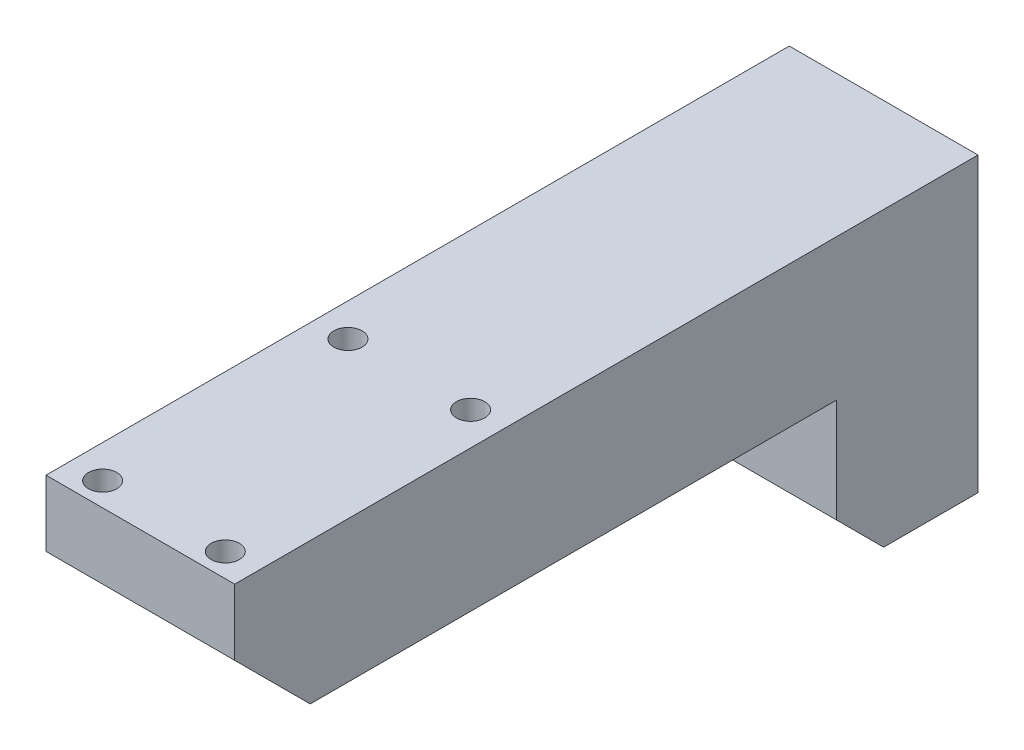
SolidWorks part; units mm, degrees
ref_plane "Płaszczyzna przednia" through (0, 0, 0) normal (0, 0, 1) x (1, 0, 0)
ref_plane "Płaszczyzna górna" through (0, 0, 0) normal (0, 1, 0) x (1, 0, 0)
ref_plane "Płaszczyzna prawa" through (0, 0, 0) normal (1, 0, 0) x (0, 0, -1)
sketch "Szkic1" plane through (0, 0, 0) normal (0, 1, 0) x (1, 0, 0)
  line L1 (20, -78.775) -> (-20, -78.775)
  line L2 (20, -78.775) -> (20, 78.775)
  line L3 (20, 78.775) -> (-20, 78.775)
  line L4 (-20, -78.775) -> (-20, 78.775)
  line L5 (20, -78.775) -> (-20, 78.775) construction
  line L6 (20, 78.775) -> (-20, -78.775) construction
  point P0 (0, 0)
  dimension "D1" = 40
  dimension "D2" = 157.55
extrude "Dodanie-wyciągnięcie1" add sketch "Szkic1" along normal blind 30
sketch "Szkic2" plane through (0, 0, 0) normal (0, -1, 0) x (-1, 0, 0)
  line L0 (20, 78.775) -> (20, -78.775) construction
  line L1 (-20, 78.775) -> (20, 78.775)
  line L2 (-20, 78.775) -> (-20, 48.775)
  line L3 (-20, 48.775) -> (20, 48.775)
  line L4 (20, 78.775) -> (20, 48.775)
  dimension "D1" = 30
extrude "Dodanie-wyciągnięcie2" add sketch "Szkic2" along normal blind 32
sketch "Szkic3" plane through (0, 30, 0) normal (0, 1, 0) x (1, 0, 0)
  line L0 (-20, -78.775) -> (20, -78.775) construction
  line L1 (-20, 78.775) -> (-20, -78.775) construction
  line L2 (20, -78.775) -> (20, 78.775) construction
  circle A0 centre (-13, -73.775) radius 3
  circle A1 centre (13, -73.775) radius 3
  circle A2 centre (13, -21.775) radius 3
  circle A3 centre (-13, -21.775) radius 3
  point P8 (0, 0)
  point P9 (0, 0)
  point P10 (0, 0)
  point P11 (0, 0)
  point P12 (0, 0)
  point P13 (0, 0)
  dimension "D1" = 6
  dimension "D2" = 5
  dimension "D3" = 7
  dimension "D4" = 7
  dimension "D5" = 52
extrude "Wytnij-wyciągnięcie1" cut sketch "Szkic3" against normal blind 30
sketch "Szkic4" plane through (0, 0, 0) normal (0, -1, 0) x (1, 0, 0)
  circle A0 centre (13, 73.775) radius 5.5
  circle A1 centre (-13, 73.775) radius 5.5
  point P6 (0, 0)
  dimension "D1" = 11
chamfer "Sfazowanie1" distance 16 angle 45 1 edges at (0, 0, 78.775)
extrude "Wytnij-wyciągnięcie7" cut sketch "Szkic4" against normal blind 15
chamfer "Sfazowanie2" distance 10 angle 45 1 edges at (0, -32, -48.775)
